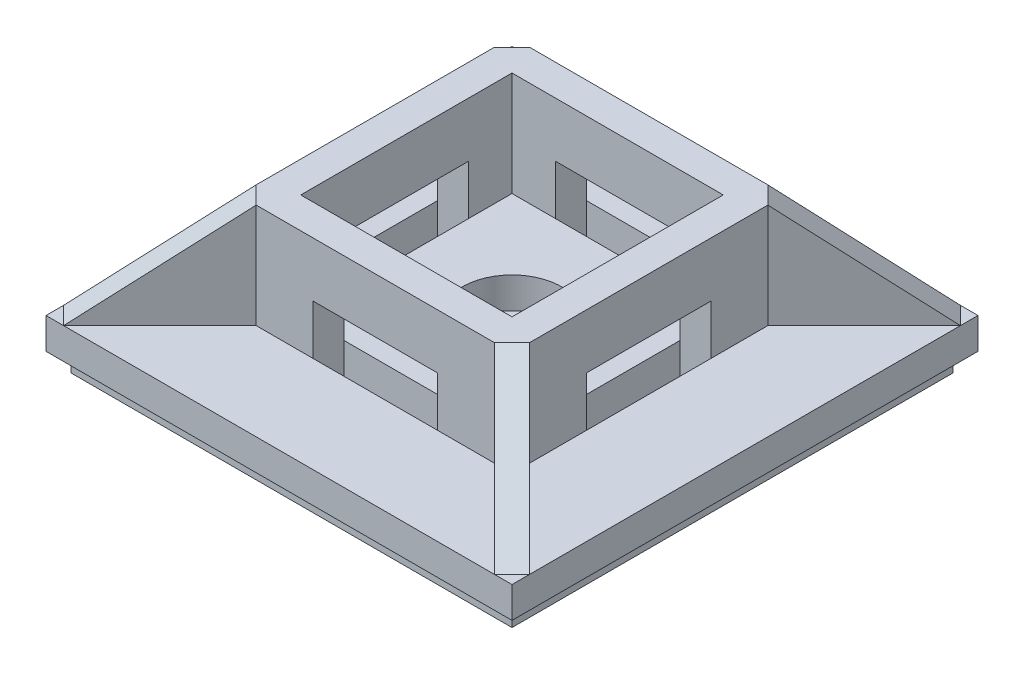
SolidWorks part; units mm, degrees
ref_plane "Front Plane" through (0, 0, 0) normal (0, 0, 1) x (1, 0, 0)
ref_plane "Top Plane" through (0, 0, 0) normal (0, 1, 0) x (1, 0, 0)
ref_plane "Right Plane" through (0, 0, 0) normal (1, 0, 0) x (0, 0, -1)
sketch "Sketch1" plane through (0, 0, 0) normal (0, 1, 0) x (1, 0, 0)
  line L1 (9.525, -9.525) -> (-9.525, -9.525)
  line L2 (9.525, -9.525) -> (9.525, 9.525)
  line L3 (9.525, 9.525) -> (-9.525, 9.525)
  line L4 (-9.525, -9.525) -> (-9.525, 9.525)
  line L5 (9.525, -9.525) -> (-9.525, 9.525) construction
  line L6 (9.525, 9.525) -> (-9.525, -9.525) construction
  line L7 (4.318, -4.318) -> (-4.318, -4.318)
  line L8 (4.318, -4.318) -> (4.318, 4.318)
  line L9 (4.318, 4.318) -> (-4.318, 4.318)
  line L10 (-4.318, -4.318) -> (-4.318, 4.318)
  line L11 (4.318, -4.318) -> (-4.318, 4.318) construction
  line L12 (4.318, 4.318) -> (-4.318, -4.318) construction
  circle A0 centre (0, 0) radius 2.032
  point P0 (0, 0)
  point P6 (0, 0)
  dimension "D3" = 4.064
  dimension "D1" = 19.05
  dimension "D2" = 19.05
  dimension "D4" = 8.636
sketch "Sketch2" plane through (0, 0, 0) normal (0, 1, 0) x (1, 0, 0)
  line L0 (-9.525, -9.525) -> (-9.525, 9.525) construction
  line L1 (9.525, -9.525) -> (-9.525, -9.525) construction
  line L2 (9.525, -9.525) -> (9.525, 9.525) construction
  line L3 (9.525, 9.525) -> (-9.525, 9.525) construction
  line L4 (-9.525, -9.525) -> (-9.525, 9.525)
  line L5 (9.525, -9.525) -> (-9.525, -9.525)
  line L6 (9.525, -9.525) -> (9.525, 9.525)
  line L7 (9.525, 9.525) -> (-9.525, 9.525)
  circle A0 centre (0, 0) radius 2.032 construction
  circle A1 centre (0, 0) radius 2.032
extrude "Boss-Extrude1" add sketch "Sketch2" along normal blind 1.27
sketch "Sketch3" plane through (0, 0, 0) normal (0, -1, 0) x (1, 0, 0)
  line L8 (9.017, 9.017) -> (-9.017, 9.017)
  line L9 (-9.017, 9.017) -> (-9.017, -9.017)
  line L10 (-9.017, -9.017) -> (9.017, -9.017)
  line L11 (9.017, -9.017) -> (9.017, 9.017)
  line L12 (9.017, 9.017) -> (-9.017, 9.017)
  line L13 (-9.017, 9.017) -> (-9.017, -9.017)
  line L14 (-9.017, -9.017) -> (9.017, -9.017)
  line L15 (9.017, -9.017) -> (9.017, 9.017)
  dimension "D1" = 0.508
extrude "Boss-Extrude2" add sketch "Sketch3" along normal blind 0.762
sketch "Sketch4" plane through (0, 0, 0) normal (0, -1, 0) x (1, 0, 0)
  line L0 (4.318, 4.318) -> (4.318, -4.318) construction
  line L1 (4.318, 4.318) -> (-4.318, 4.318) construction
  line L2 (-4.318, 4.318) -> (-4.318, -4.318) construction
  line L3 (4.318, -4.318) -> (-4.318, -4.318) construction
  line L4 (4.318, 4.318) -> (4.318, -4.318)
  line L5 (4.318, 4.318) -> (-4.318, 4.318)
  line L6 (-4.318, 4.318) -> (-4.318, -4.318)
  line L7 (4.318, -4.318) -> (-4.318, -4.318)
  line L8 (5.588, 5.588) -> (5.588, -5.588)
  line L9 (5.588, -5.588) -> (-5.588, -5.588)
  line L10 (-5.588, 5.588) -> (-5.588, -5.588)
  line L11 (5.588, 5.588) -> (-5.588, 5.588)
  dimension "D1" = 1.27
extrude "Boss-Extrude3" add sketch "Sketch4" against normal blind 5.5372
sketch "Sketch5" plane through (5.588, 0, 0) normal (1, 0, 0) x (0, 0, -1)
  line L0 (-9.525, 1.27) -> (9.525, 1.27) construction
  line L1 (-2.54, 1.27) -> (2.54, 1.27)
  line L2 (-2.54, 1.27) -> (-2.54, 3.302)
  line L3 (-2.54, 3.302) -> (2.54, 3.302)
  line L4 (2.54, 1.27) -> (2.54, 3.302)
  line L5 (0, 0) -> (0, 1.27) construction
  dimension "D1" = 2.032
  dimension "D2" = 5.08
extrude "Cut-Extrude1" cut sketch "Sketch5" against normal through all
sketch "Sketch6" plane through (0, 0, -5.588) normal (0, 0, -1) x (-1, 0, 0)
  line L0 (0, 0) -> (0, 1.27) construction
  line L1 (-2.54, 3.302) -> (2.54, 3.302)
  line L2 (-2.54, 3.302) -> (-2.54, 1.27)
  line L3 (-2.54, 1.27) -> (2.54, 1.27)
  line L4 (2.54, 3.302) -> (2.54, 1.27)
  line L5 (5.588, 1.27) -> (-5.588, 1.27) construction
  dimension "D1" = 5.08
extrude "Cut-Extrude2" cut sketch "Sketch6" against normal through all
sketch "Sketch7" plane through (0, 1.27, 0) normal (0, 1, 0) x (1, 0, 0)
  line L0 (-4.318, -4.318) -> (-4.318, -2.54) construction
  line L1 (5.588, -2.54) -> (4.318, -2.54)
  line L2 (5.588, -2.54) -> (5.588, 2.54)
  line L3 (5.588, 2.54) -> (4.318, 2.54)
  line L4 (4.318, -2.54) -> (4.318, 2.54)
  line L5 (-2.54, 5.588) -> (2.54, 5.588)
  line L6 (-2.54, 5.588) -> (-2.54, 4.318)
  line L7 (-2.54, 4.318) -> (2.54, 4.318)
  line L8 (2.54, 5.588) -> (2.54, 4.318)
  line L9 (2.54, -4.318) -> (-2.54, -4.318)
  line L10 (2.54, -4.318) -> (2.54, -5.588)
  line L11 (2.54, -5.588) -> (-2.54, -5.588)
  line L12 (-2.54, -4.318) -> (-2.54, -5.588)
  line L13 (-5.588, -2.54) -> (-4.318, -2.54)
  line L14 (-5.588, -2.54) -> (-5.588, 2.54)
  line L15 (-5.588, 2.54) -> (-4.318, 2.54)
  line L16 (-4.318, -2.54) -> (-4.318, 2.54)
  line L17 (-5.588, -2.54) -> (-4.318, -2.54) construction
extrude "Cut-Extrude3" cut sketch "Sketch7" against normal up to vertex (1.27 mm away) up to point (9.525, 0, -9.525)
sketch "Sketch8" plane through (0, 1.27, 0) normal (0, 1, 0) x (1, 0, 0)
  line L0 (-8.8066, 9.525) -> (-9.525, 8.8066)
  line L1 (-8.8066, 9.525) -> (-4.8696, 5.588)
  line L2 (-9.525, 8.8066) -> (-5.588, 4.8696)
  line L3 (-4.8696, 5.588) -> (-5.588, 4.8696)
  line L16 (9.525, 9.525) -> (-9.525, 9.525) construction
  line L17 (-9.525, 9.525) -> (-9.525, -9.525) construction
  line L18 (-5.588, 5.588) -> (5.588, 5.588) construction
  line L19 (-5.588, -5.588) -> (-5.588, 5.588) construction
  dimension "D1" = 1.016
extrude "Boss-Extrude4" add sketch "Sketch8" along normal up to vertex (4.2672 mm away) separate body up to point (-5.588, 5.5372, 5.588)
sketch "Sketch10" plane through (-0.3592, 0, 0.3592) normal (-0.7071, 0, 0.7071) x (0.7071, 0, 0.7071)
  line L0 (-12.9624, 1.27) -> (-7.3946, 5.5372)
  line L1 (0, 5.5372) -> (-7.9026, 5.5372) construction
  line L2 (-7.3946, 5.5372) -> (-12.9624, 5.5372)
  line L3 (-12.9624, 5.5372) -> (-12.9624, 1.27)
  line L4 (-7.3946, 5.5372) -> (-7.3946, 1.27) construction
extrude "Cut-Extrude5" cut sketch "Sketch10" against normal through all
ref_axis "Axis1" through (0, -1.077, 0) along (0, 1, 0)
pattern_circular "CirPattern1" count 4 over 360 about axis through (0, -1.077, 0) along (0, 1, 0) of bodies 117
sketch "Sketch9" plane through (0, 5.5372, 0) normal (0, 1, 0) x (1, 0, 0)
  line L4 (-5.588, -5.588) -> (5.588, -5.588)
  line L5 (5.588, -5.588) -> (5.588, 5.588)
  line L6 (5.588, 5.588) -> (-4.8696, 5.588)
  line L7 (-5.588, 4.8696) -> (-5.588, -5.588)
  line L8 (-5.588, -5.588) -> (5.588, -5.588)
  line L9 (5.588, -5.588) -> (5.588, 5.588)
  line L10 (5.588, 5.588) -> (-4.8696, 5.588)
  line L11 (-5.588, 4.8696) -> (-5.588, -5.588)
  line L13 (-4.8696, 5.588) -> (-5.588, 4.8696)
  line L14 (-4.8696, 5.588) -> (-5.588, 4.8696)
  dimension "D1" = 0
combine bodies "Combine1" operation type add bodies to combine 117 116 118 119 120
other "DeleteFace1" face at (-5.588, 5.4074, 5.3485) face at (-5.3485, 5.4074, 5.588) face at (5.3485, 5.4074, 5.588) face at (5.588, 5.4074, 5.3485) face at (5.588, 5.4074, -5.3485) face at (5.3485, 5.4074, -5.588) and patch yes
